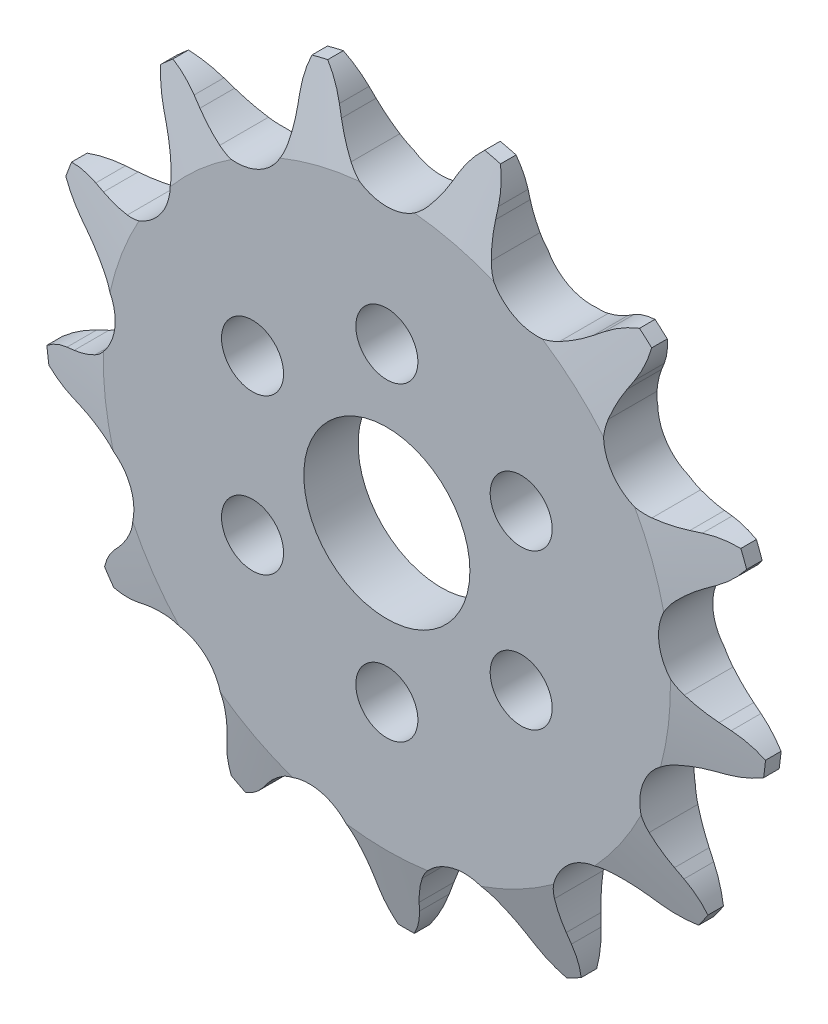
SolidWorks part; units mm, degrees
material "AISI 4130 Steel, annealed at 865C"
ref_plane "Front Plane" through (0, 0, 0) normal (0, 0, 1) x (1, 0, 0)
ref_plane "Top Plane" through (0, 0, 0) normal (0, 1, 0) x (1, 0, 0)
ref_plane "Right Plane" through (0, 0, 0) normal (1, 0, 0) x (0, 0, -1)
sketch "Sketch0" plane through (0, 0, 0) normal (0, 0, 1) x (1, 0, 0)
  line L0 (7.9375, -32.2037) -> (0, 0) construction
  line L1 (0, 0) -> (21.9941, -24.8262) construction
  line L2 (0, 0) -> (-7.9375, -32.2037) construction
  line L3 (7.9375, -32.2037) -> (21.9941, -24.8262) construction
  line L4 (7.9375, -32.2037) -> (-7.9375, -32.2037) construction
  line L5 (13.9545, -31.0679) -> (13.2815, -30.2592)
  line L6 (7.9375, -32.2037) -> (0, -34.1601) construction
  line L7 (2.0819, -33.9942) -> (2.302, -32.9654)
  line L8 (0, -32.2037) -> (0, -36.9662) construction
  line L9 (10.986, -28.0897) -> (3.0984, -38.7342) construction
  line L10 (0, 0) -> (0, -32.2037) construction
  line L11 (13.2815, -30.2592) -> (3.0984, -38.7342) construction
  line L12 (0, -36.9662) -> (0, -38.0102) construction
  line L13 (20.5322, -25.5935) -> (13.9545, -31.0679) construction
  circle A0 centre (0, 0) radius 36.9662 construction
  circle A1 centre (0, 0) radius 33.1675 construction
  arc A2 (-7.9261, -40.603) -> (25.8874, -32.2687) centre (0, 0) ccw
  circle A3 centre (0, 0) radius 38.0102 construction
  circle A4 centre (7.9375, -32.2037) radius 5.08 construction
  arc A7 (10.986, -28.0897) -> (3.3263, -29.9776) centre (7.9375, -32.2037) ccw
  circle A8 centre (7.9375, -32.2037) radius 5.1204 construction
  arc A9 (13.9545, -31.0679) -> (25.8874, -32.2687) centre (20.5322, -25.5935) ccw
  arc A10 (13.2815, -30.2592) -> (10.986, -28.0897) centre (3.0984, -38.7342) ccw
  arc A11 (2.0819, -33.9942) -> (-7.9261, -40.603) centre (-6.2865, -32.2037) cw
  arc A12 (2.302, -32.9654) -> (3.3263, -29.9776) centre (15.2572, -35.7373) cw
  dimension "D1" = 5.1204
  dimension "R" = 5.1204
sketch "Sketch1" plane through (0, 0, 0) normal (1, 0, 0) x (0, 0, -1)
  line L0 (2.7781, 0) -> (-2.7781, 0)
  line L1 (-2.7781, 0) -> (-2.7781, 29.0287)
  line L2 (-2.7781, 29.0287) -> (-0.7937, 36.9662)
  line L3 (-0.7937, 36.9662) -> (0.7937, 36.9662)
  line L4 (0.7937, 36.9662) -> (2.7781, 29.0287)
  line L5 (2.7781, 29.0287) -> (2.7781, 0)
  line L7 (0, 36.9662) -> (0, 0) construction
  line L8 (-2.7781, 29.0287) -> (2.7781, 29.0287) construction
  line L9 (0, 36.9662) -> (0, -36.9662) construction
  line L10 (-2.7781, 29.0287) -> (-2.7781, 36.9662) construction
  line L11 (-2.7781, 36.9662) -> (-0.7937, 36.9662) construction
  line L12 (0.7937, 36.9662) -> (2.7781, 36.9662) construction
  line L13 (2.7781, 36.9662) -> (2.7781, 29.0287) construction
revolve "Revolve1" add sketch "Sketch1" angle 360 mid plane about L0
extrude "Cut-Extrude1" cut sketch "Sketch0" against normal through all and the other way through all
pattern_circular "CirPattern1" count 13 over 360 about axis through (0, 0, -2.7781) along (0, 0, -1) of "Cut-Extrude1"
sketch "Sketch2" plane through (0, 0, 0) normal (0, 0, 1) x (1, 0, 0)
  circle A0 centre (0, 0) radius 7.9375 construction
  circle A1 centre (0, 0) radius 30.1625
  circle A2 centre (0, 0) radius 36.957 construction
  dimension "Bore" = 15.875
  dimension "Hub Dia." = 60.325
  dimension "OD" = 73.914
sketch "Sketch3" plane through (0, 0, 0) normal (0, 0, 1) x (1, 0, 0)
  circle A1 centre (0, 0) radius 8.5
  circle A2 centre (0, 0) radius 36.957 construction
  circle A3 centre (0, 0) radius 36.957
  dimension "D1" = 17
extrude "Cut-Extrude2" cut sketch "Sketch3" along normal through all and the other way through all flip side to cut
sketch "Sketch4" plane through (0, 0, -2.7781) normal (0, 0, -1) x (-1, 0, 0)
  line L0 (0, 0) -> (0, 15.875) construction
  circle A0 centre (0, 15.875) radius 3.175
  circle A1 centre (13.7482, 7.9375) radius 3.175
  circle A2 centre (13.7482, -7.9375) radius 3.175
  circle A3 centre (0, -15.875) radius 3.175
  circle A4 centre (-13.7482, -7.9375) radius 3.175
  circle A5 centre (-13.7482, 7.9375) radius 3.175
  point P17 (0, 0)
  dimension "D1" = 6
extrude "Cut-Extrude3" cut sketch "Sketch4" against normal through all
sketch "Sketch5" plane through (0, 0, 2.7781) normal (0, 0, 1) x (1, 0, 0)
  line L0 (0, 0) -> (8.5, 0) construction
  line L1 (8.5, 0) -> (11, 0) construction
  circle A0 centre (0, 0) radius 11 construction
  circle A1 centre (0, 0) radius 8.5 construction
sketch "Sketch6" plane through (0, 0, -2.7781) normal (0, 0, -1) x (-1, 0, 0)
  circle A0 centre (0, 0) radius 28.024 construction
  circle A1 centre (0, 0) radius 24.2521 construction
ref_plane "Plane1" through (-29.6883, 20.4924, 0) normal (-0.823, 0.5681, 0) x (0, 0, 1)
ref_plane "Plane2" through (-35.811, 4.3482, 0) normal (-0.9927, 0.1205, 0) x (0, 0, 1)
ref_plane "Plane3" through (-33.7298, -12.792, 0) normal (-0.935, -0.3546, 0) x (0, 0, 1)
ref_plane "Plane4" through (-23.9215, -27.0018, 0) normal (-0.6631, -0.7485, 0) x (-0.7485, 0.6631, 0)
ref_plane "Plane5" through (-8.6331, -35.0258, 0) normal (-0.2393, -0.9709, 0) x (-0.9709, 0.2393, 0)
sketch "Sketch7" plane through (-29.6883, 20.4924, 0) normal (-0.823, 0.5681, 0) x (0, 0, 1)
  line L0 (-6.5106, 0) -> (7.7601, 0)
sketch "Sketch8" plane through (-35.811, 4.3482, 0) normal (-0.9927, 0.1205, 0) x (0, 0, 1)
  line L0 (-7.786, 0) -> (10.2102, 0)
sketch "Sketch9" plane through (-33.7298, -12.792, 0) normal (-0.935, -0.3546, 0) x (0, 0, 1)
  line L0 (-7.6671, 0) -> (14.0341, 0)
  line L1 (-2.7781, 0) -> (2.7781, 0) construction
sketch "Sketch10" plane through (-23.9215, -27.0018, 0) normal (-0.6631, -0.7485, 0) x (-0.7485, 0.6631, 0)
  line L0 (0, -3.5829) -> (0, 5.4944)
sketch "Sketch11" plane through (-8.6331, -35.0258, 0) normal (-0.2393, -0.9709, 0) x (-0.9709, 0.2393, 0)
  line L0 (0, -5.4358) -> (0, 8.5188)
split line "Split Line7"
split line "Split Line8"
split line "Split Line9"
split line "Split Line10"
split line "Split Line11"
ref_plane "Motor Sprocket Middle Plane" through (0, 0, 1.6781) normal (0, 0, 1) x (1, 0, 0)
equation "\"360/N@Sketch0\" = 360/\"Teeth@CirPattern1\""
equation "\"Ds@Sketch0\" = 1.005 * \"Dr@Sketch0\" + 0.003"
equation "\"R@Sketch0\" = 1/2 * \"Ds@Sketch0\""
equation "\"A@Sketch0\" = 35 +  ( 60 / \"Teeth@CirPattern1\" ) "
equation "\"B@Sketch0\" = 18 -  ( 56 / \"Teeth@CirPattern1\" )"
equation "\"ac@Sketch0\" = 0.8 * \"Dr@Sketch0\""
equation "\"ab@Sketch0\" = 1.4 * \"Dr@Sketch0\""
equation "\"J@Sketch0\" = 0.3 * \"Pitch@Sketch0\""
equation "\"h@Sketch1\" = \"Pitch@Sketch0\" / 2"
equation "\"g@Sketch1\" = \"h@Sketch1\" / 4"
